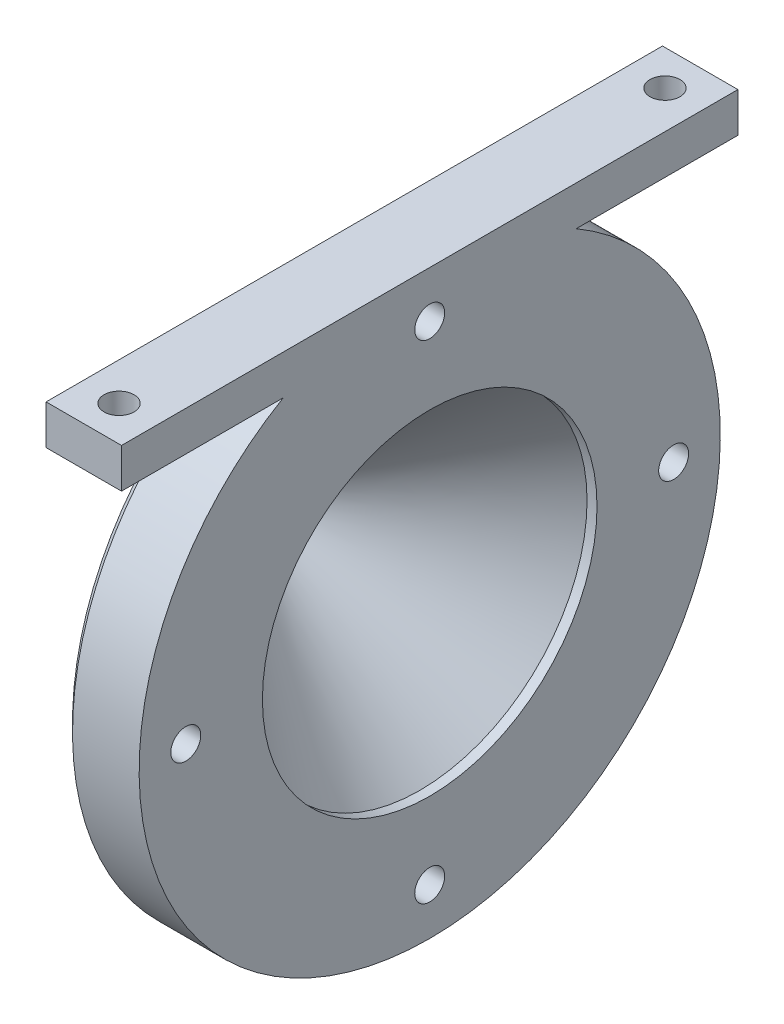
SolidWorks part; units mm, degrees
ref_plane "Front Plane" through (0, 0, 0) normal (0, 0, 1) x (1, 0, 0)
ref_plane "Top Plane" through (0, 0, 0) normal (0, 1, 0) x (1, 0, 0)
ref_plane "Right Plane" through (0, 0, 0) normal (1, 0, 0) x (0, 0, -1)
sketch "Sketch1" plane through (0, 0, 0) normal (0, 0, 1) x (1, 0, 0)
  line L0 (-801.9271, 0) -> (36107.5217, 0) construction
  line L3 (-14.0102, 3.8) -> (-14.0102, 3.15)
  line L8 (-18.3435, 1.9) -> (0, 1.9)
  line L9 (-18.3435, 1.9) -> (-18.3435, 3.15)
  line L10 (19.9465, 24.5) -> (19.9465, 33)
  line L12 (19.9465, 33) -> (11.3805, 33)
  line L18 (11.3805, 33) -> (11.3805, 19)
  line L20 (0, 1.9) -> (18.8145, 19)
  line L21 (-18.3435, 3.15) -> (-14.0102, 3.8)
  line L23 (-14.0102, 3.15) -> (-9.6768, 3.8)
  line L25 (-9.6768, 3.15) -> (-5.3435, 3.8)
  line L26 (-9.6768, 3.8) -> (-9.6768, 3.15)
  line L27 (-5.3435, 3.8) -> (11.3805, 19)
  line L28 (11.3805, 28.5) -> (19.9465, 28.5)
  line L32 (19.9465, 24.5) -> (19.9465, 19)
  line L33 (19.9465, 19) -> (18.8145, 19)
  line L35 (19.9465, 24.5) -> (20.5125, 24.5) construction
  line L36 (11.3805, 33) -> (19.9465, 33)
  point P14 (0, 0)
  point P17 (0, 0)
  point P18 (0, 0)
  point P20 (19.9465, 24.5)
  dimension "D5" = 33
  dimension "D2" = 7.6
  dimension "D4" = 5
  dimension "D6" = 3.8
  dimension "D7" = 6.3
  dimension "D11" = 13
  dimension "D12" = 8.566
  dimension "D13" = 4.5
revolve "Revolve17" add sketch "Sketch1" angle 360 about L0
extrude "Boss-Extrude1" add sketch "Sketch1<11>" against normal mid plane 70 contours L18 L28 L10 L12 region at (15.6635, 30.75, 0)
sketch "Sketch1<11>" plane through (0, 0, 0) normal (0, 0, 1) x (1, 0, 0) same geometry as "Sketch1"
sketch "Sketch4" plane through (11.3805, 0, 0) normal (-1, 0, 0) x (0, 0, 1)
  circle A0 centre (0, 0) radius 27.7 construction
  circle A2 centre (0, 0) radius 33 construction
  point P3 (0, 27.7)
  point P7 (27.7, 0)
  point P12 (-27.7, 0)
  point P13 (0, -27.7)
  point P27 (0, -27.7)
  dimension "D1" = 5.3
hole_wizard "M3 Clearance Hole1" positions "Sketch4" profile "Sketch5" hole size "M3" standard "ISO"
sketch "Sketch5" plane through (11.3805, -27.7, 0) normal (0, 1, 0) x (0, 0, 1)
  line L0 (0, 0) -> (0, 9.5875)
  line L1 (0, 9.5875) -> (1.7, 8.566)
  line L2 (1.7, 8.566) -> (1.7, 0)
  line L5 (1.7, 0) -> (0, 0)
  line L10 (0, 9.5875) -> (-1.7, 8.566) construction
  line L11 (0, -6.35) -> (0, 107.95) construction
  dimension "Hole Dia." = 3.4
  dimension "Hole Depth" = 8.566
  dimension "Drill Angle" = 118
chamfer "Chamfer1" distance 1 angle 45 1 edges at (11.3805, -33, 0)
sketch "Sketch9" plane through (0, 28.5, 0) normal (0, -1, 0) x (-1, 0, 0)
  line L0 (-11.3805, -35) -> (-19.9465, 35) construction
  line L1 (-11.3805, -14.5516) -> (-11.3805, -35) construction
  line L2 (-11.3805, -35) -> (-19.9465, -35) construction
  line L3 (-19.9465, 35) -> (-19.9465, 16.6358) construction
  line L4 (-19.9465, 35) -> (-11.3805, 35) construction
  line L5 (-11.3805, 35) -> (-19.9465, 35) construction
  line L6 (-11.3805, 35) -> (-19.9465, -35) construction
  line L7 (-19.9465, -16.6358) -> (-19.9465, -35) construction
  line L8 (-15.6635, -35) -> (-15.6635, 35) construction
  line L9 (-4.5963, 0) -> (-19.9465, 0) construction
  line L10 (-19.9465, 33) -> (-19.9465, -33) construction
  circle A0 centre (-15.6635, -31) radius 1.7
  circle A1 centre (-15.6635, 31) radius 1.7
  dimension "D1" = 3.4
  dimension "D2" = 4
extrude "Cut-Extrude1" cut sketch "Sketch9" against normal blind 10
sketch "Sketch10" plane through (11.3805, 0, 0) normal (-1, 0, 0) x (0, 0, 1)
  line L0 (37, 0) -> (19, 0)
  line L1 (-19, 0) -> (-37, 0)
  line L2 (0, -19) -> (0, -37)
  circle A1 centre (0, 0) radius 19 construction
  point P15 (0, 30.467)
